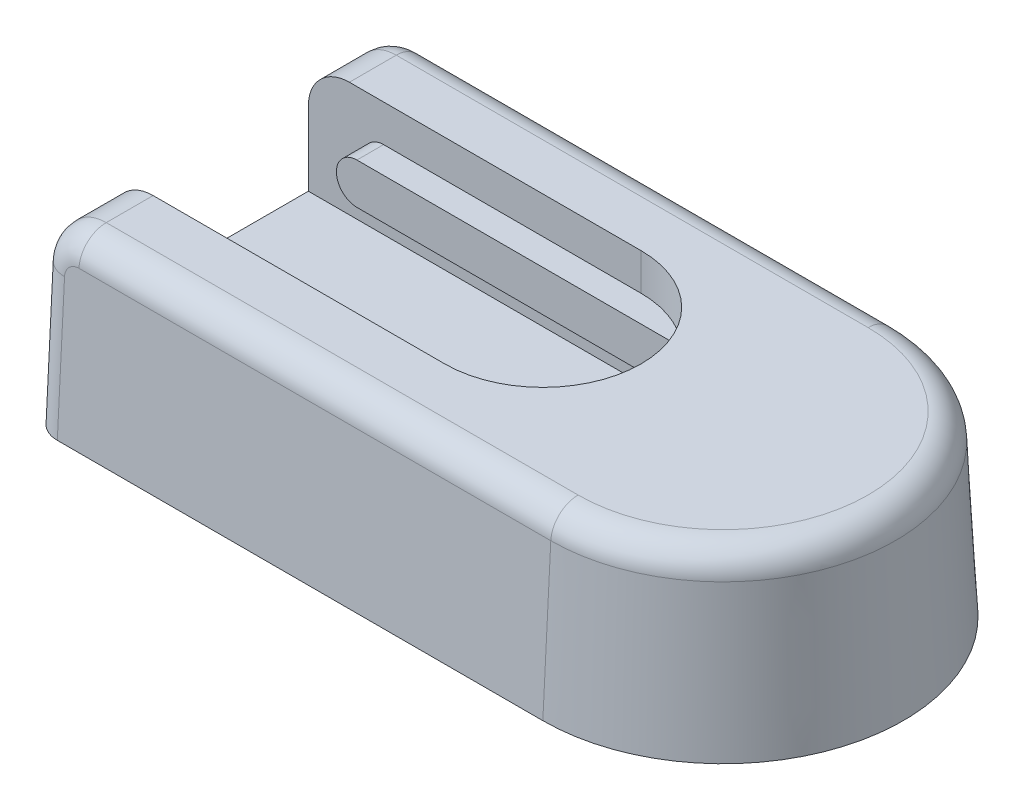
SolidWorks part; units mm, degrees
ref_plane "Front Plane" through (0, 0, 0) normal (0, 0, 1) x (1, 0, 0)
ref_plane "Top Plane" through (0, 0, 0) normal (0, 1, 0) x (1, 0, 0)
ref_plane "Right Plane" through (0, 0, 0) normal (1, 0, 0) x (0, 0, -1)
sketch "Sketch1" plane through (0, 0, 0) normal (0, 1, 0) x (1, 0, 0)
  line L0 (0, 0) -> (37.5, 0)
  line L1 (0, 0) -> (0, 25)
  line L2 (0, 25) -> (37.5, 25)
  arc A0 (37.5, 25) -> (37.5, 0) centre (37.5, 12.5) cw
  point P5 (50, 12.5)
  dimension "D1" = 25
  dimension "D2" = 50
extrude "Boss-Extrude1" add sketch "Sketch1" along normal blind 13
sketch "Sketch2" plane through (0, 13, 0) normal (0, 1, 0) x (1, 0, 0)
  line L0 (0, 19.675) -> (24.325, 19.675)
  line L1 (0, 25) -> (0, 0) construction
  line L2 (0, 19.675) -> (0, 5.325)
  line L3 (0, 5.325) -> (24.325, 5.325)
  line L4 (0, 25) -> (0, 0)
  arc A0 (24.325, 5.325) -> (24.325, 19.675) centre (24.325, 12.5) ccw
  point P4 (0, 12.5)
  point P7 (0, 12.5)
  point P9 (31.5, 12.5)
  line M3 (0, 25) -> (0, 0)
  dimension "D2" = 31.5
  dimension "D1" = 14.35
extrude "Cut-Extrude1" cut sketch "Sketch2" against normal blind 8.4 contours L3 A0 L0 M3 region at (15.0229, 13, -12.5)
sketch "Sketch3" plane through (0, 4.6, 0) normal (0, 1, 0) x (1, 0, 0)
  line L0 (0, 5.325) -> (24.325, 5.325) construction
  line L1 (0, 19.675) -> (24.325, 19.675) construction
  line L2 (4, 5.325) -> (24.325, 5.325)
  line L3 (4, 19.675) -> (24.325, 19.675)
  line L6 (29.2423, 17.725) -> (4, 17.725)
  line L7 (-968.5, 12.5) -> (49031.5, 12.5) construction
  line L8 (29.2423, 7.275) -> (4, 7.275)
  line L9 (4, 7.275) -> (4, 5.325)
  line L11 (4, 17.725) -> (4, 19.675)
  arc A0 (24.325, 5.325) -> (24.325, 19.675) centre (24.325, 12.5) ccw construction
  arc A1 (24.325, 5.325) -> (29.2423, 7.275) centre (24.325, 12.5) ccw
  arc A2 (29.2423, 17.725) -> (24.325, 19.675) centre (24.325, 12.5) ccw
  dimension "D1" = 1.95
  dimension "D2" = 4
extrude "Boss-Extrude3" add sketch "Sketch3" along normal blind 3 from offset 2.7
fillet "Fillet1" radius 1.5 4 edges at (4, 7.3, -6.3) (4, 10.3, -6.3) (4, 7.3, -18.7) (4, 10.3, -18.7)
draft "Draft2" type of draft neutral plane draft angle 3 faces to draft 3 face at (18.75, 6.5, -25) face at (43.75, 6.5, -12.5) face at (18.75, 6.5, 0) neutral plane through (37.5, 13, -12.5) neutral plane normal (0, 1, 0) parameters "D1"=3
fillet "Fillet2" radius 3 2 edges at (0, 13, -22.3375) (0, 13, -2.6625)
fillet "Fillet3" radius 2 7 edges at (0, 5, 0.4193) (0.8787, 12.1213, 0.046) (0, 5, -25.4193) (0.8787, 12.1213, -25.046) (20.25, 13, -25) (50, 13, -12.5) (20.25, 13, 0)
